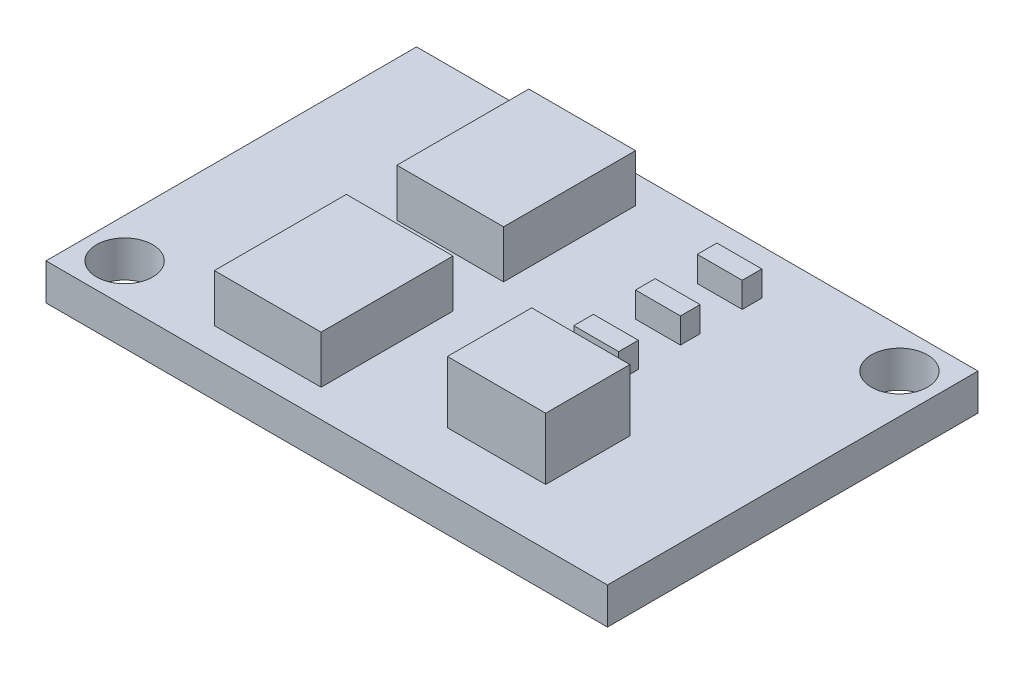
SolidWorks part; units mm, degrees
ref_plane "前视基准面" through (0, 0, 0) normal (0, 0, 1) x (1, 0, 0)
ref_plane "上视基准面" through (0, 0, 0) normal (0, 1, 0) x (1, 0, 0)
ref_plane "右视基准面" through (0, 0, 0) normal (1, 0, 0) x (0, 0, -1)
other "Configuration Table"
sketch "草图1" plane through (0, 0, 0) normal (0, 1, 0) x (1, 0, 0)
  line L5 (-10, 6.6) -> (10, 6.6)
  line L6 (-10, 6.6) -> (-10, -6.6)
  line L7 (-10, -6.6) -> (10, -6.6)
  line L8 (10, 6.6) -> (10, -6.6)
  line L9 (-10, 6.6) -> (10, -6.6) construction
  line L10 (-10, -6.6) -> (10, 6.6) construction
  line L11 (-5, 5.6) -> (-1.2, 5.6)
  line L12 (-5, 5.6) -> (-5, 0.9)
  line L13 (-5, 0.9) -> (-1.2, 0.9)
  line L14 (-1.2, 5.6) -> (-1.2, 0.9)
  line L15 (-5, -0.9) -> (-1.2, -0.9)
  line L16 (-5, -0.9) -> (-5, -5.6)
  line L17 (-5, -5.6) -> (-1.2, -5.6)
  line L18 (-1.2, -0.9) -> (-1.2, -5.6)
  line L19 (2.3, 5) -> (3.9, 5)
  line L20 (2.3, 5) -> (2.3, 4.3)
  line L21 (2.3, 4.3) -> (3.9, 4.3)
  line L22 (3.9, 5) -> (3.9, 4.3)
  line L23 (2.3, 2.8) -> (3.9, 2.8)
  line L24 (2.3, 2.8) -> (2.3, 2.1)
  line L25 (2.3, 2.1) -> (3.9, 2.1)
  line L26 (3.9, 2.8) -> (3.9, 2.1)
  line L27 (2.3, 0.6) -> (3.9, 0.6)
  line L28 (2.3, 0.6) -> (2.3, -0.1)
  line L29 (2.3, -0.1) -> (3.9, -0.1)
  line L30 (3.9, 0.6) -> (3.9, -0.1)
  line L31 (2.3, -1.6) -> (5.8, -1.6)
  line L32 (2.3, -1.6) -> (2.3, -4.6)
  line L33 (2.3, -4.6) -> (5.8, -4.6)
  line L34 (5.8, -1.6) -> (5.8, -4.6)
  circle A0 centre (8.6, 5.2) radius 1
  circle A1 centre (-8.6, -5.2) radius 1
  point P0 (0, 0)
  dimension "D7" = 2
  dimension "D1" = 20
  dimension "D2" = 13.2
  dimension "D3" = 1.4
  dimension "D4" = 1.4
  dimension "D5" = 1.4
  dimension "D6" = 1.4
  dimension "D8" = 3.8
  dimension "D9" = 4.7
  dimension "D10" = 1
  dimension "D11" = 5
  dimension "D12" = 1
  dimension "D13" = 5
  dimension "D14" = 0.7
  dimension "D15" = 1.6
  dimension "D16" = 3
  dimension "D17" = 3.5
  dimension "D18" = 3.5
  dimension "D19" = 2
  dimension "D20" = 1.5
  dimension "D21" = 1.5
  dimension "D22" = 1.5
extrude "凸台-拉伸1" add sketch "草图1" along normal blind 1.3 contours A0 | A1 | L5 L8 L7 L6 region at (8.6, 0, -5.2) region at (-8.6, 0, 5.2)
extrude "凸台-拉伸2" add sketch "草图1<3>" along normal blind 3 contours L12 L13 L14 L11 | L16 L17 L18 L15
sketch "草图1<3>" plane through (0, 0, 0) normal (0, 1, 0) x (1, 0, 0) same geometry as "草图1"
extrude "凸台-拉伸3" add sketch "草图1<4>" along normal blind 2.2 contours L19 L22 L21 L20 | L23 L26 L25 L24 | L27 L30 L29 L28
sketch "草图1<4>" plane through (0, 0, 0) normal (0, 1, 0) x (1, 0, 0) same geometry as "草图1"
extrude "凸台-拉伸4" add sketch "草图1<5>" along normal blind 3.5 contours L31 L34 L33 L32
sketch "草图1<5>" plane through (0, 0, 0) normal (0, 1, 0) x (1, 0, 0) same geometry as "草图1"
